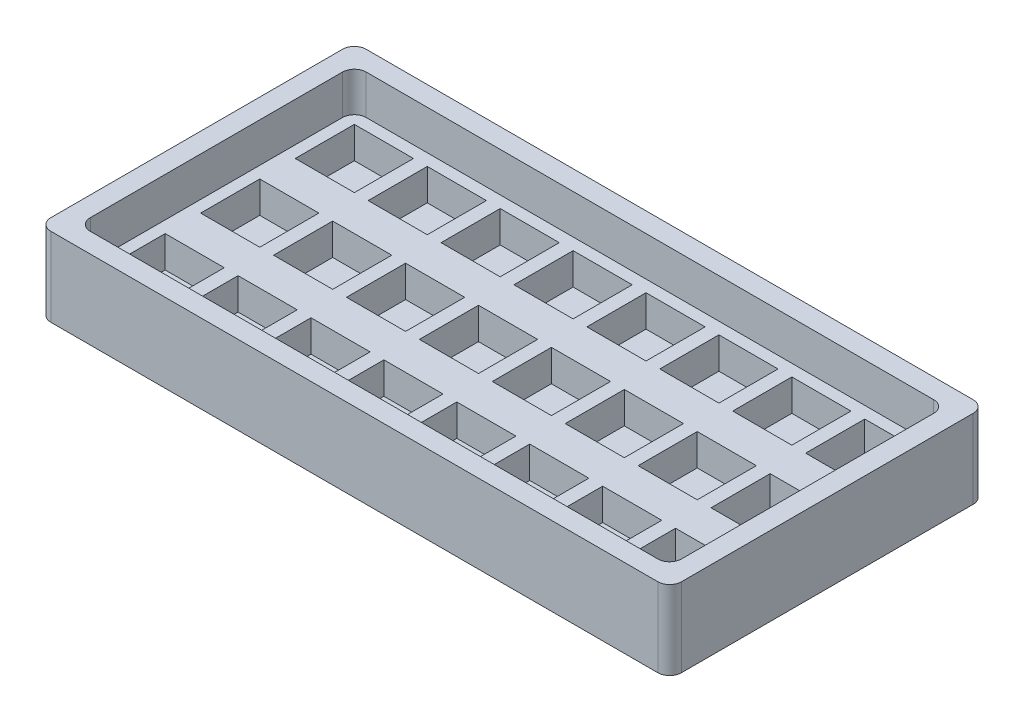
SolidWorks part; units mm, degrees
ref_plane "Front Plane" through (0, 0, 0) normal (0, 0, 1) x (1, 0, 0)
ref_plane "Top Plane" through (0, 0, 0) normal (0, 1, 0) x (1, 0, 0)
ref_plane "Right Plane" through (0, 0, 0) normal (1, 0, 0) x (0, 0, -1)
sketch "Sketch1" plane through (0, 0, 0) normal (0, 1, 0) x (1, 0, 0)
  line L0 (0, 55.5086) -> (0, -52.0289) construction
  line L1 (-72, 35) -> (72, 35)
  line L2 (-75, 32) -> (-75, -32)
  line L3 (-72, -35) -> (72, -35)
  line L4 (75, 32) -> (75, -32)
  line L5 (-75, 35) -> (75, -35) construction
  line L6 (-75, -35) -> (75, 35) construction
  line L7 (92.0815, 0) -> (-89.5596, 0) construction
  line L8 (-53.5, 17) -> (-38.5, 17)
  line L9 (-77, 40) -> (77, 40)
  line L10 (-80, 37) -> (-80, -37)
  line L11 (-77, -40) -> (77, -40)
  line L12 (80, 37) -> (80, -37)
  line L13 (-80, 40) -> (80, -40) construction
  line L14 (-80, -40) -> (80, 40) construction
  line L15 (-72, 32) -> (-57, 32)
  line L16 (-72, 32) -> (-72, 17)
  line L17 (-72, 17) -> (-57, 17)
  line L18 (-57, 32) -> (-57, 17)
  line L19 (-53.5, 32) -> (-53.5, 17)
  line L20 (-53.5, 32) -> (-38.5, 32)
  line L21 (-38.5, 32) -> (-38.5, 17)
  line L22 (-35, 17) -> (-20, 17)
  line L23 (-35, 32) -> (-35, 17)
  line L24 (-35, 32) -> (-20, 32)
  line L25 (-20, 32) -> (-20, 17)
  line L26 (-16.5, 17) -> (-1.5, 17)
  line L27 (-16.5, 32) -> (-16.5, 17)
  line L28 (-16.5, 32) -> (-1.5, 32)
  line L29 (-1.5, 32) -> (-1.5, 17)
  line L30 (2, 17) -> (17, 17)
  line L31 (2, 32) -> (2, 17)
  line L32 (2, 32) -> (17, 32)
  line L33 (17, 32) -> (17, 17)
  line L34 (20.5, 17) -> (35.5, 17)
  line L35 (20.5, 32) -> (20.5, 17)
  line L36 (20.5, 32) -> (35.5, 32)
  line L37 (35.5, 32) -> (35.5, 17)
  line L38 (39, 17) -> (54, 17)
  line L39 (39, 32) -> (39, 17)
  line L40 (39, 32) -> (54, 32)
  line L41 (54, 32) -> (54, 17)
  line L42 (57.5, 17) -> (72.5, 17)
  line L43 (57.5, 32) -> (57.5, 17)
  line L44 (57.5, 32) -> (72.5, 32)
  line L45 (72.5, 32) -> (72.5, 17)
  line L46 (-53.5, -7) -> (-38.5, -7)
  line L47 (-53.5, 8) -> (-53.5, -7)
  line L48 (-53.5, 8) -> (-38.5, 8)
  line L49 (-38.5, 8) -> (-38.5, -7)
  line L50 (-35, -7) -> (-20, -7)
  line L51 (-35, 8) -> (-35, -7)
  line L52 (-35, 8) -> (-20, 8)
  line L53 (-20, 8) -> (-20, -7)
  line L54 (-16.5, -7) -> (-1.5, -7)
  line L55 (-16.5, 8) -> (-16.5, -7)
  line L56 (-16.5, 8) -> (-1.5, 8)
  line L57 (-1.5, 8) -> (-1.5, -7)
  line L58 (2, -7) -> (17, -7)
  line L59 (2, 8) -> (2, -7)
  line L60 (2, 8) -> (17, 8)
  line L61 (17, 8) -> (17, -7)
  line L62 (20.5, -7) -> (35.5, -7)
  line L63 (20.5, 8) -> (20.5, -7)
  line L64 (20.5, 8) -> (35.5, 8)
  line L65 (35.5, 8) -> (35.5, -7)
  line L66 (39, -7) -> (54, -7)
  line L67 (39, 8) -> (39, -7)
  line L68 (39, 8) -> (54, 8)
  line L69 (54, 8) -> (54, -7)
  line L70 (57.5, -7) -> (72.5, -7)
  line L71 (57.5, 8) -> (57.5, -7)
  line L72 (57.5, 8) -> (72.5, 8)
  line L73 (72.5, 8) -> (72.5, -7)
  line L74 (-53.5, -31) -> (-38.5, -31)
  line L75 (-53.5, -16) -> (-53.5, -31)
  line L76 (-53.5, -16) -> (-38.5, -16)
  line L77 (-38.5, -16) -> (-38.5, -31)
  line L78 (-35, -31) -> (-20, -31)
  line L79 (-35, -16) -> (-35, -31)
  line L80 (-35, -16) -> (-20, -16)
  line L81 (-20, -16) -> (-20, -31)
  line L82 (-16.5, -31) -> (-1.5, -31)
  line L83 (-16.5, -16) -> (-16.5, -31)
  line L84 (-16.5, -16) -> (-1.5, -16)
  line L85 (-1.5, -16) -> (-1.5, -31)
  line L86 (2, -31) -> (17, -31)
  line L87 (2, -16) -> (2, -31)
  line L88 (2, -16) -> (17, -16)
  line L89 (17, -16) -> (17, -31)
  line L90 (20.5, -31) -> (35.5, -31)
  line L91 (20.5, -16) -> (20.5, -31)
  line L92 (20.5, -16) -> (35.5, -16)
  line L93 (35.5, -16) -> (35.5, -31)
  line L94 (39, -31) -> (54, -31)
  line L95 (39, -16) -> (39, -31)
  line L96 (39, -16) -> (54, -16)
  line L97 (54, -16) -> (54, -31)
  line L98 (57.5, -31) -> (72.5, -31)
  line L99 (57.5, -16) -> (57.5, -31)
  line L100 (57.5, -16) -> (72.5, -16)
  line L101 (72.5, -16) -> (72.5, -31)
  line L102 (-72, -7) -> (-57, -7)
  line L103 (-72, 8) -> (-72, -7)
  line L104 (-72, 8) -> (-57, 8)
  line L105 (-57, 8) -> (-57, -7)
  line L106 (-72, -31) -> (-57, -31)
  line L107 (-72, -16) -> (-72, -31)
  line L108 (-72, -16) -> (-57, -16)
  line L109 (-57, -16) -> (-57, -31)
  arc A0 (72, -35) -> (75, -32) centre (72, -32) ccw
  arc A1 (72, 35) -> (75, 32) centre (72, 32) cw
  arc A2 (-75, -32) -> (-72, -35) centre (-72, -32) ccw
  arc A3 (-72, 35) -> (-75, 32) centre (-72, 32) ccw
  arc A4 (-80, -37) -> (-77, -40) centre (-77, -37) ccw
  arc A5 (77, -40) -> (80, -37) centre (77, -37) ccw
  arc A6 (77, 40) -> (80, 37) centre (77, 37) cw
  arc A7 (-77, 40) -> (-80, 37) centre (-77, 37) ccw
  point P0 (0, 0)
  point P22 (0, 0)
  dimension "D3" = 3
  dimension "D6" = 3
  dimension "D1" = 70
  dimension "D2" = 150
  dimension "D4" = 80
  dimension "D5" = 160
  dimension "D7" = 15
  dimension "D8" = 15
  dimension "D9" = 3
  dimension "D10" = 3
  dimension "D11" = 8
  dimension "D12" = 3
extrude "Boss-Extrude1" add sketch "Sketch1" along normal blind 8 contours L1 A3 L2 A2 L3 A0 L4 A1 L108 L109 L106 L107 L104 L105 L102 L103 L100 L101 L98 L99 L96 L97 L94 L95 L92 L93 L90 L91 L88 L89 L86 L87 L84 L85 L82 L83 L80 L81 L78 L79 L76 L77 | L9 A7 L10 A4 L11 A5 L12 A6 A3 L1 A1 L4 A0 L3 A2 L2 region at (-0.2651, 0, 0.5302) region at (0, 0, -38.2111)
extrude "Boss-Extrude2" add sketch "Sketch1<3>" along normal blind 18 contours L3 A0 L4 A1 L1 A3 L2 A2 | L12 A5 L11 A4 L10 A7 L9 A6
sketch "Sketch1<3>" plane through (0, 0, 0) normal (0, 1, 0) x (1, 0, 0) same geometry as "Sketch1"
extrude "Boss-Extrude3" add sketch "Sketch1<4>" against normal blind 2 contours L9 A6 L12 A5 L11 A4 L10 A7
sketch "Sketch1<4>" plane through (0, 0, 0) normal (0, 1, 0) x (1, 0, 0) same geometry as "Sketch1"
